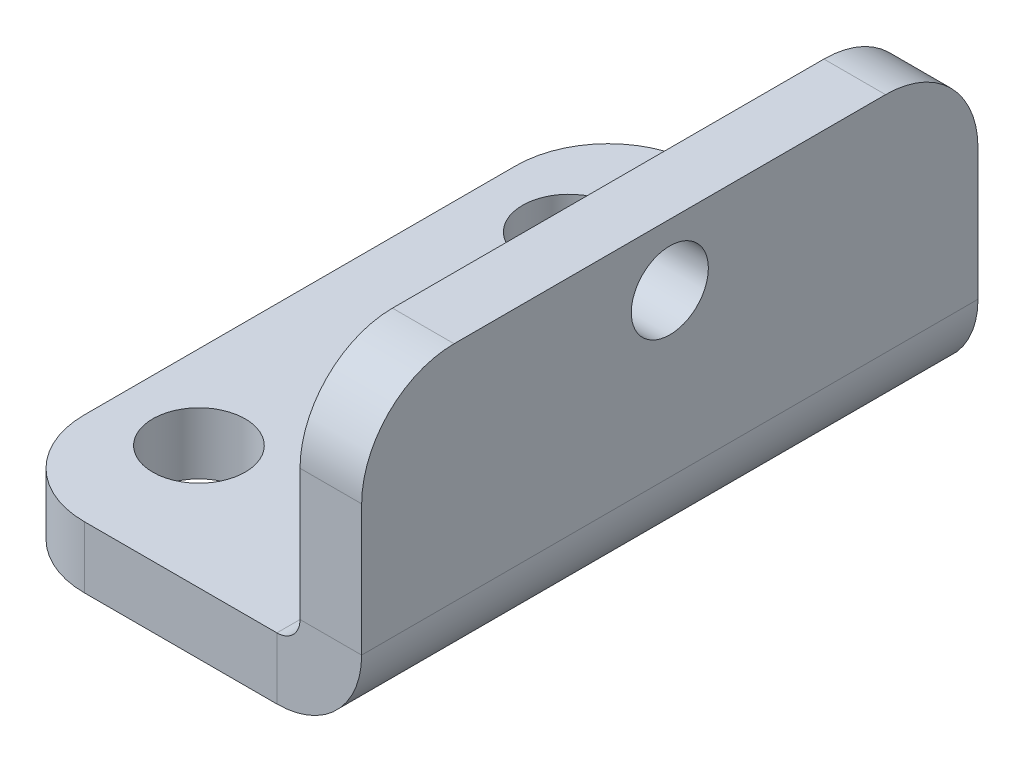
SolidWorks part; units mm, degrees
note: The reader was unsure of these and kept them because the rebuilt part matched: flange length of "Edge-Flange1".
ref_plane "Front Plane" through (0, 0, 0) normal (0, 0, 1) x (1, 0, 0)
ref_plane "Top Plane" through (0, 0, 0) normal (0, 1, 0) x (1, 0, 0)
ref_plane "Right Plane" through (0, 0, 0) normal (1, 0, 0) x (0, 0, -1)
sketch "Sketch1" plane through (0, 0, 0) normal (0, 1, 0) x (1, 0, 0)
  line L0 (0, 7) -> (0, -7)
  line L1 (3, 10) -> (12, 10)
  line L2 (3, -10) -> (12, -10)
  line L3 (12, 10) -> (12, -10)
  arc A0 (0, -7) -> (3, -10) centre (3, -7) ccw
  arc A1 (0, 7) -> (3, 10) centre (3, 7) cw
  circle A2 centre (2.72, 6) radius 1.5
  circle A3 centre (2.72, -6) radius 1.5
  point P0 (0, 6)
  point P4 (0, 0)
  point P8 (0, -6)
  point P11 (0, -10)
  point P14 (0, 10)
  dimension "D6" = 3
  dimension "D7" = 3
  dimension "D8" = 3
  dimension "D1" = 20
  dimension "D2" = 12
  dimension "D3" = 12
  dimension "D4" = 6
  dimension "D5" = 12
  dimension "D9" = 9.28
  dimension "D10" = 9.28
base flange "Base-Flange1" sketch "Sketch1" thickness 2 reverse thickness direction yes parameters "D1"=0.7366
edge flange "Edge-Flange1" sketch "Sketch8" flange angle 90 flange length 10 flange position material inside bend radius 0.75 thickness 2 relief rectangular parameters "D6"=10
sketch "Sketch8" plane through (12, 2, 0) normal (1, 0, 0) x (0, 0, -1)
  line L2 (-10, 0) -> (-10, 8)
  line L3 (-10, 8) -> (10, 8)
  line L4 (10, 8) -> (10, 0)
  line L7 (-10, 0) -> (10, 0) construction
  line L8 (-10, 0) -> (10, 0)
  dimension "D1" = 8
bend "EdgeBend1" bend radius 0.75 bend angle 90 parameters "D5"=1
sketch "Sketch9" plane through (10, 0, 0) normal (-1, 0, 0) x (0, 0, 1)
  line L0 (-10, 10) -> (10, 10) construction
  circle A0 centre (0, 8) radius 1.25
  dimension "D1" = 2
  dimension "D2" = 2.5
extrude "Cut-Extrude1" cut sketch "Sketch9" against normal blind 10 normal cut yes
fillet "Fillet1" radius 3 2 edges at (11, 10, 10) (11, 10, -10)
sketch "Bend-Lines1" [suppressed] plane through (0, 0, 0) normal (0, 1, 0) x (1, 0, 0)
sketch "Bounding-Box1" [suppressed] plane through (0, 0, 0) normal (0, 1, 0) x (1, 0, 0)
sheet metal parameters "Sheet-Metal1" thickness 2 parameters "D1"=0.7366
flat pattern "Flat-Pattern1" [suppressed]
sketch "Bend-Lines2" plane through (0, 0, 0) normal (0, 1, 0) x (1, 0, 0)
sketch3d "Bounding-Box2" [suppressed]
  line L0 (-3, 17, 0) -> (-3, -3, 0) construction
  line L1 (9, 17, 0) -> (9, -3, 0) construction
  line L2 (-3, 17, 0) -> (9, 17, 0) construction
  line L3 (-3, -3, 0) -> (9, -3, 0) construction
sheet metal parameters "Sheet-Metal2" thickness 2 parameters "D1"=0.7366
flat pattern "Flat-Pattern1"
sketch "Bend-Lines2" plane through (0, 0, 0) normal (0, -1, 0) x (-1, 0, 0)
  line L0 (-10.6244, 10) -> (-10.6244, -10) construction
  line L1 (-10.6244, 10) -> (-10.6244, -10) construction
sketch3d "Bounding-Box2" [suppressed]
  line L0 (3, 17, 0) -> (3, -3, 0) construction
  line L1 (-14.2489, 17, 0) -> (-14.2489, -3, 0) construction
  line L2 (3, 17, 0) -> (-14.2489, 17, 0) construction
  line L3 (3, -3, 0) -> (-14.2489, -3, 0) construction
bend of the flat pattern "Flatten-<EdgeBend1>1"
sheet metal parameters "Sheet-Metal3" thickness 2 parameters "D1"=0.7366
flat pattern "Flat-Pattern1"
sketch "Bend-Lines2" plane through (0, 0, 0) normal (0, -1, 0) x (-1, 0, 0)
  line L0 (-10.6244, 10) -> (-10.6244, -10) construction
  line L1 (-10.6244, 10) -> (-10.6244, -10) construction
sketch3d "Bounding-Box2" [suppressed]
  line L0 (-16.2489, 17, 0) -> (-16.2489, -3, 0) construction
  line L1 (3, 17, 0) -> (3, -3, 0) construction
  line L2 (-16.2489, 17, 0) -> (3, 17, 0) construction
  line L3 (-16.2489, -3, 0) -> (3, -3, 0) construction
bend of the flat pattern "Flatten-<EdgeBend1>1"
